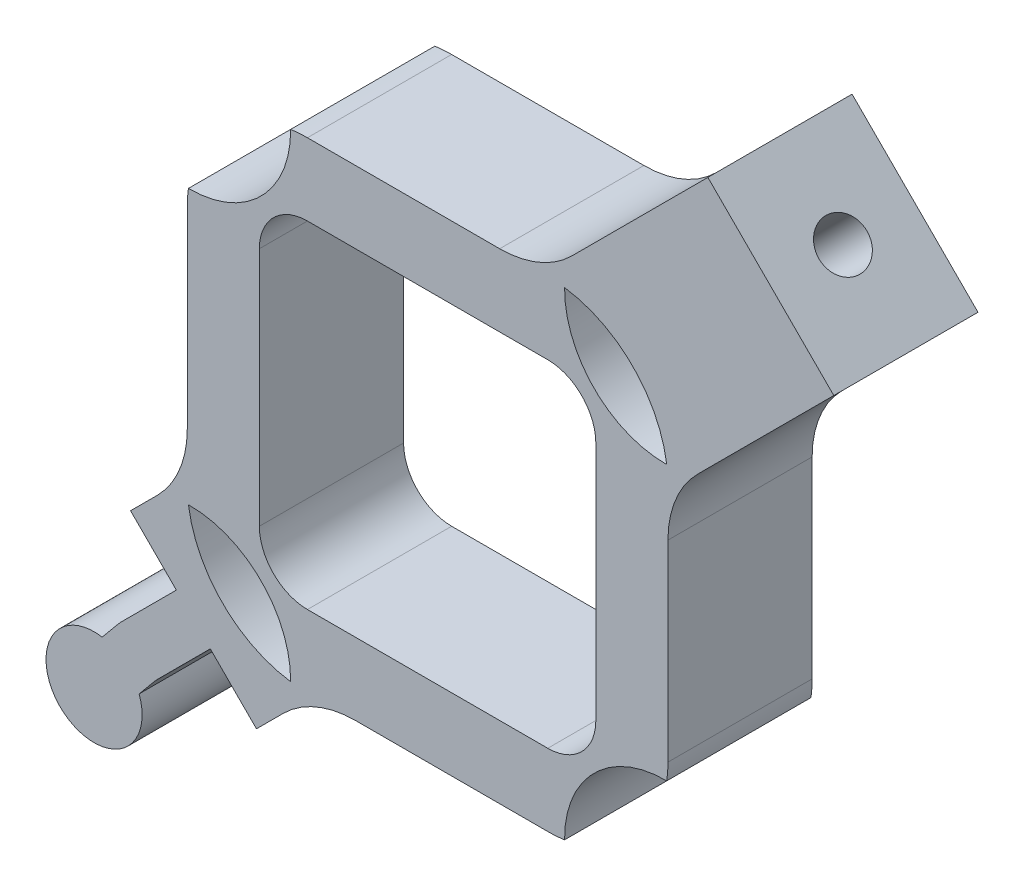
SolidWorks part; units mm, degrees
ref_plane "前视基准面" through (0, 0, 0) normal (0, 0, 1) x (1, 0, 0)
ref_plane "上视基准面" through (0, 0, 0) normal (0, 1, 0) x (1, 0, 0)
ref_plane "右视基准面" through (0, 0, 0) normal (1, 0, 0) x (0, 0, -1)
sketch "草图1" plane through (0, 0, 0) normal (0, 0, 1) x (1, 0, 0)
  line L0 (-5, 2.5) -> (-5, -2.5)
  line L1 (-2.5, 3.5) -> (2.5, 3.5)
  line L2 (-3.5, 2.5) -> (-3.5, -2.5)
  line L3 (-2.5, -3.5) -> (2.5, -3.5)
  line L4 (3.5, 2.5) -> (3.5, -2.5)
  line L5 (-3.5, 3.5) -> (3.5, -3.5) construction
  line L6 (-3.5, -3.5) -> (3.5, 3.5) construction
  line L7 (-2.5, -5) -> (2.5, -5)
  line L8 (5, 2.5) -> (5, -2.5)
  line L9 (-2.5, 5) -> (2.5, 5)
  line L10 (1.5, 5) -> (1.5, 7.9864) construction
  line L11 (1.5, 7.125) -> (3.0026, 5.6224) construction
  line L12 (3.0026, 5.6224) -> (5.831, 8.4508)
  line L13 (5.6224, 3.0026) -> (8.4508, 5.831)
  line L14 (5.831, 8.4508) -> (8.4508, 5.831)
  line L15 (-8.4508, -5.831) -> (-5.831, -8.4508)
  line L16 (-3.0026, -5.6224) -> (-5.831, -8.4508)
  line L17 (-5.6224, -3.0026) -> (-8.4508, -5.831)
  arc A0 (-3.5, -2.5) -> (-2.5, -3.5) centre (-2.5, -2.5) ccw
  arc A1 (2.5, -3.5) -> (3.5, -2.5) centre (2.5, -2.5) ccw
  arc A2 (3.5, 2.5) -> (2.5, 3.5) centre (2.5, 2.5) ccw
  arc A3 (-2.5, 3.5) -> (-3.5, 2.5) centre (-2.5, 2.5) ccw
  arc A4 (-5, -2.5) -> (-2.5, -5) centre (-2.5, -2.5) ccw
  arc A5 (2.5, -5) -> (2.8499, -4.9754) centre (2.5, -2.5) ccw
  arc A6 (5, 2.5) -> (2.5, 5) centre (2.5, 2.5) ccw
  arc A7 (-2.5, 5) -> (-2.8499, 4.9754) centre (-2.5, 2.5) ccw
  arc A8 (-4.9754, 2.8499) -> (-2.8499, 4.9754) centre (-4.9497, 4.9497) ccw
  arc A9 (-4.9754, 2.8499) -> (-5, 2.5) centre (-2.5, 2.5) ccw
  arc A10 (-2.5, 5) -> (-5, 2.5) centre (-2.5, 2.5) ccw construction
  arc A11 (4.9754, -2.8499) -> (2.8499, -4.9754) centre (4.9497, -4.9497) ccw
  arc A12 (4.9754, -2.8499) -> (5, -2.5) centre (2.5, -2.5) ccw
  arc A13 (2.5, -5) -> (5, -2.5) centre (2.5, -2.5) ccw construction
  arc A14 (2.8499, 4.9754) -> (4.9754, 2.8499) centre (4.9497, 4.9497) ccw
  arc A15 (-4.9754, -2.8499) -> (-2.8499, -4.9754) centre (-4.9497, -4.9497) cw
  arc A16 (1.5, 5) -> (3.0026, 5.6224) centre (1.5, 7.125) ccw
  arc A17 (5, 1.5) -> (5.6224, 3.0026) centre (7.125, 1.5) cw
  arc A18 (-1.5, -5) -> (-3.0026, -5.6224) centre (-1.5, -7.125) ccw
  arc A19 (-5, -1.5) -> (-5.6224, -3.0026) centre (-7.125, -1.5) cw
  point P0 (0, 0)
  dimension "D3" = 1
  dimension "D6" = 4.2
  dimension "D7" = 4.2
  dimension "D9" = 4.2
  dimension "D12" = 4.25
  dimension "D1" = 7
  dimension "D2" = 7
  dimension "D5" = 7
  dimension "D8" = 7
  dimension "D10" = 7
  dimension "D11" = 1
  dimension "D13" = 45
  dimension "D14" = 4
  dimension "D4" = 1.5
extrude "凸台-拉伸1" add sketch "草图1" along normal blind 3 contours A4 A15 L7 A5 A11 A12 L8 A6 A14 L9 A7 A8 A9 L0 A3 L1 A2 L4 A1 L3 A0 L2 | L0 A19 L17 L15 L16 A18 L7 A4 | L8 A17 L13 L14 L12 A16 L9 A6 region at (-4.8528, 2.6655, 0) region at (-5.5878, -5.5878, 0) region at (5.5878, 5.5878, 0)
sketch "草图4" plane through (-7.1409, -7.1409, 0) normal (-0.7071, -0.7071, 0) x (0, 0, 1)
  line L4 (0, 1.8525) -> (0, -1.8525)
  line L5 (0, -1.8525) -> (3, -1.8525)
  line L6 (3, -1.8525) -> (3, 1.8525)
  line L7 (3, 1.8525) -> (0, 1.8525)
  line L8 (0, 1.8525) -> (0, -1.8525)
  line L9 (0, -1.8525) -> (3, -1.8525)
  line L10 (3, -1.8525) -> (3, 1.8525)
  line L11 (3, 1.8525) -> (0, 1.8525)
  dimension "D1" = 0
extrude "凸台-拉伸3" add sketch "草图4" along normal blind 1
sketch "草图6" plane through (7.1409, 7.1409, 0) normal (0.7071, 0.7071, 0) x (0, 0, -1)
  line L0 (-3, 0) -> (0, 0) construction
  line L1 (-3, 1.8525) -> (-3, -1.8525) construction
  circle A0 centre (-1.5, 0) radius 0.5
  dimension "D1" = 1
extrude "切除-拉伸2" cut sketch "草图6" against normal up to next
ref_plane "基准面1" through (0, 0, 1.5) normal (0, 0, 1) x (1, 0, 0)
ref_axis "基准轴1" through (3.8512, 3.8512, 1.5) along (0.7071, 0.7071, 0)
sketch "草图7" plane through (0, 0, 0) normal (0, 0, -1) x (-1, 0, 0)
  line L0 (7.5773, -7.8886) -> (6.2301, -9.0055) construction
  line L1 (7.5773, -7.8886) -> (6.2301, -9.0055)
  line L2 (7.5773, -7.8886) -> (5.2439, -5.0743) construction
  line L3 (6.0014, -6.7712) -> (5.6822, -6.3863)
  line L4 (6.7712, -6.1329) -> (6.4521, -5.748)
  line L5 (5.6822, -6.3863) -> (5.2251, -6.7653) construction
  line L6 (7.848, -7.848) -> (2.8507, -2.8507) construction
  line L7 (9.1579, -6.5381) -> (6.5381, -9.1579) construction
  line L8 (5.6195, -6.3174) -> (4.5211, -5.219)
  line L9 (6.358, -5.6448) -> (5.2266, -4.5134)
  line L10 (4.5211, -5.219) -> (5.2266, -4.5134)
  line L11 (4.5211, -5.219) -> (3.5601, -6.1799)
  line L12 (3.0026, -5.6224) -> (6.5381, -9.1579) construction
  line L13 (3.5601, -6.1799) -> (6.5381, -9.1579)
  line L14 (6.5381, -9.1579) -> (9.1579, -6.5381)
  line L15 (5.219, -4.5211) -> (6.1799, -3.5601)
  line L16 (6.1799, -3.5601) -> (9.1579, -6.5381)
  circle A0 centre (6.939, -7.1187) radius 1
  circle A1 centre (4.9124, -7.0246) radius 1
  circle A2 centre (5.2973, -6.7054) radius 1.5
  line M18 (3.0026, -5.6224) -> (6.5381, -9.1579)
  line M19 (6.5381, -9.1579) -> (9.1579, -6.5381)
  line M20 (9.1579, -6.5381) -> (5.6224, -3.0026)
  dimension "D1" = 2
  dimension "D3" = 2
  dimension "D4" = 3
  dimension "D2" = 0.5
  dimension "D5" = 1.6
extrude "切除-拉伸3" cut sketch "草图7" against normal blind 3 contours A2 L4 A0 L1 L15 L9 M18 M19 M20 | A2 L13 L1 A0 | A2 A0 L3 A1 M18 | A1 L13 | L8 A2 L13 A1 | A2 L8 L11 M18 region at (-7.1749, -5.7157, 0) region at (-6.384, -8.3433, 0) region at (-5.8254, -7.7197, 0) region at (-5.0811, -6.8559, 0) region at (-4.4904, -5.9233, 0) region at (-4.0252, -5.8526, 0)
